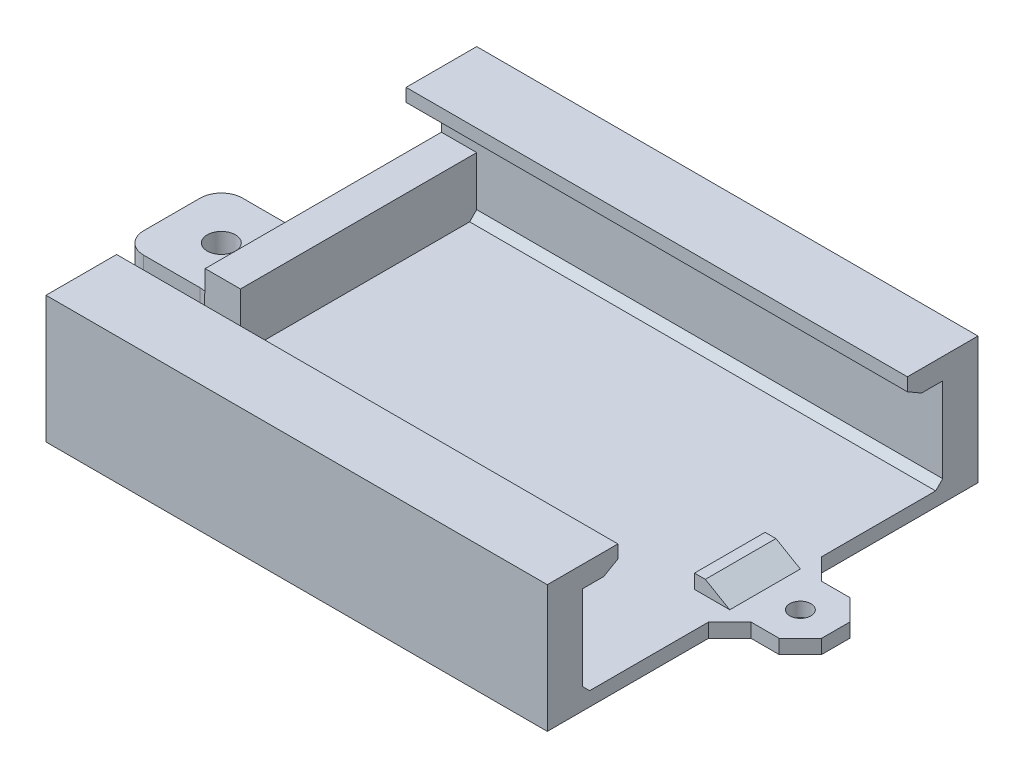
SolidWorks part; units mm, degrees
ref_plane "Front Plane" through (0, 0, 0) normal (0, 0, 1) x (1, 0, 0)
ref_plane "Top Plane" through (0, 0, 0) normal (0, 1, 0) x (1, 0, 0)
ref_plane "Right Plane" through (0, 0, 0) normal (1, 0, 0) x (0, 0, -1)
sketch "Sketch1" plane through (0, 0, 0) normal (0, 1, 0) x (1, 0, 0)
  line L1 (-30.5, -25.5) -> (30.5, -25.5)
  line L2 (-30.5, -25.5) -> (-30.5, 25.5)
  line L3 (-30.5, 25.5) -> (30.5, 25.5)
  line L4 (30.5, -25.5) -> (30.5, 25.5)
  line L5 (-30.5, -25.5) -> (30.5, 25.5) construction
  line L6 (-30.5, 25.5) -> (30.5, -25.5) construction
  line L7 (-35.5, -30.5) -> (35.5, -30.5)
  line L8 (-35.5, -30.5) -> (-35.5, 30.5)
  line L9 (-35.5, 30.5) -> (35.5, 30.5)
  line L10 (35.5, -30.5) -> (35.5, 30.5)
  line L11 (-35.5, -30.5) -> (35.5, 30.5) construction
  line L12 (-35.5, 30.5) -> (35.5, -30.5) construction
  point P0 (0, 0)
  point P6 (0, 0)
  dimension "D1" = 61
  dimension "D2" = 51
  dimension "D3" = 5
  dimension "D4" = 5
extrude "Boss-Extrude1" add sketch "Sketch1" along normal blind 16
sketch "Sketch2" plane through (0, 0, 0) normal (0, -1, 0) x (1, 0, 0)
  line L1 (-35.5, -30.5) -> (35.5, -30.5)
  line L2 (-35.5, -30.5) -> (-35.5, 30.5)
  line L3 (-35.5, 30.5) -> (35.5, 30.5)
  line L4 (35.5, -30.5) -> (35.5, 30.5)
  line L5 (-35.5, -30.5) -> (35.5, 30.5) construction
  line L6 (-35.5, 30.5) -> (35.5, -30.5) construction
  point P0 (0, 0)
extrude "Boss-Extrude2" add sketch "Sketch2" along normal blind 2
sketch "Sketch3" plane through (-30.5, 0, 0) normal (1, 0, 0) x (0, 0, -1)
  line L0 (25.5, 16) -> (-25.5, 16) construction
  line L1 (-19.8095, 16) -> (-7.9597, 16)
  line L2 (-19.8095, 16) -> (-19.8095, 0)
  line L3 (-19.8095, 0) -> (-7.9597, 0)
  line L4 (-7.9597, 16) -> (-7.9597, 0)
  line L5 (25.5, 0) -> (-25.5, 0) construction
extrude "Cut-Extrude1" cut sketch "Sketch3" against normal blind 12
fillet "Fillet1" radius 3 2 edges at (-33, 0, 19.8095) (-33, 0, 7.9597)
sketch "Sketch4" plane through (30.5, 0, 0) normal (-1, 0, 0) x (0, 0, 1)
  line L0 (25.5, 16) -> (-25.5, 16) construction
  line L1 (-25.5, 0) -> (-10.5, 0)
  line L2 (-25.5, 0) -> (-25.5, 16)
  line L3 (-25.5, 16) -> (-10.5, 16)
  line L4 (-10.5, 0) -> (-10.5, 16)
  line L6 (25.5, 0) -> (10.5, 0)
  line L7 (25.5, 0) -> (25.5, 16)
  line L8 (25.5, 16) -> (10.5, 16)
  line L9 (10.5, 0) -> (10.5, 16)
  dimension "D1" = 15
  dimension "D2" = 15
extrude "Cut-Extrude2" cut sketch "Sketch4" against normal blind 12
sketch "Sketch5" plane through (30.5, 0, 0) normal (-1, 0, 0) x (0, 0, 1)
  line L0 (10.5, 16) -> (10.5, 0) construction
  line L1 (-10.5, 16) -> (10.5, 16)
  line L2 (-10.5, 16) -> (-10.5, 8)
  line L3 (-10.5, 8) -> (10.5, 8)
  line L4 (10.5, 16) -> (10.5, 8)
extrude "Cut-Extrude3" cut sketch "Sketch5" against normal blind 12
sketch "Sketch6" plane through (-30.5, 0, 0) normal (1, 0, 0) x (0, 0, -1)
  line L0 (25.5, 16) -> (25.5, 0) construction
  line L1 (-25.5, 16) -> (25.5, 16)
  line L2 (-25.5, 16) -> (-25.5, 8)
  line L3 (-25.5, 8) -> (25.5, 8)
  line L4 (25.5, 16) -> (25.5, 8)
extrude "Cut-Extrude4" cut sketch "Sketch6" against normal blind 12
chamfer "Chamfer1" distance 1 angle 45 2 edges at (2.5, 0, 25.5) (2.5, 0, -25.5)
sketch "Sketch8" plane through (30.5, 0, 0) normal (-1, 0, 0) x (0, 0, 1)
  line L1 (10.5, 8) -> (-10.5, 8)
  line L2 (10.5, 8) -> (10.5, 0)
  line L3 (10.5, 0) -> (-10.5, 0)
  line L4 (-10.5, 8) -> (-10.5, 0)
extrude "Cut-Extrude5" cut sketch "Sketch8" against normal blind 14
sketch "Sketch9" plane through (0, 0, -25.5) normal (0, 0, 1) x (1, 0, 0)
  line L0 (35.5, 16) -> (35.5, 1) construction
  line L1 (-35.5, 16) -> (35.5, 16)
  line L2 (-35.5, 16) -> (-35.5, 13)
  line L3 (-35.5, 13) -> (35.5, 13)
  line L4 (35.5, 16) -> (35.5, 13)
  line L5 (35.5, 0) -> (-30.5, 0) construction
  dimension "D1" = 13
extrude "Boss-Extrude4" add sketch "Sketch9" along normal blind 5
chamfer "Chamfer3" distance 2 angle 30 1 edges at (0, 13, -20.5) first distance on face at (0, 13, -23)
sketch "Sketch10" plane through (0, 0, 25.5) normal (0, 0, -1) x (-1, 0, 0)
  line L0 (-35.5, 1) -> (-35.5, 16) construction
  line L1 (35.5, 16) -> (-35.5, 16)
  line L2 (35.5, 16) -> (35.5, 13)
  line L3 (35.5, 13) -> (-35.5, 13)
  line L4 (-35.5, 16) -> (-35.5, 13)
  line L5 (30.5, 0) -> (-35.5, 0) construction
  dimension "D1" = 13
extrude "Boss-Extrude5" add sketch "Sketch10" along normal blind 5
chamfer "Chamfer4" distance 2 angle 30 1 edges at (0, 13, 20.5) first distance on face at (0, 13, 23)
sketch "Sketch11" plane through (0, 0, 0) normal (0, 1, 0) x (1, 0, 0)
  line L0 (35.5, 24.5) -> (35.5, -24.5) construction
  line L1 (35.5, -4.6573) -> (30.5, -4.6573)
  line L2 (35.5, -4.6573) -> (35.5, 5.3427)
  line L3 (35.5, 5.3427) -> (30.5, 5.3427)
  line L4 (30.5, -4.6573) -> (30.5, 5.3427)
  point P6 (35.5, 0.3427)
  dimension "D1" = 5
  dimension "D2" = 5
extrude "Boss-Extrude6" add sketch "Sketch11" along normal blind 2
chamfer "Chamfer5" distance 2 angle 60 1 edges at (35.5, 2, -0.3427) first distance on face at (35.5, 7.3155, -0.0685)
sketch "Sketch12" plane through (-35.5, 0, 0) normal (-1, 0, 0) x (0, 0, 1)
  line L0 (30.5, -2) -> (-30.5, -2) construction
  line L1 (-8.3327, -2) -> (5.6673, -2)
  line L2 (-8.3327, -2) -> (-8.3327, 3)
  line L3 (-8.3327, 3) -> (5.6673, 3)
  line L4 (5.6673, -2) -> (5.6673, 3)
  point P6 (-1.3327, -2)
  dimension "D1" = 7
  dimension "D2" = 5
extrude "Boss-Extrude7" add sketch "Sketch12" along normal blind 14
chamfer "Chamfer6" distance 2 angle 45 1 edges at (-35.5, 3, -1.3327)
sketch "Sketch13" plane through (0, 3, 0) normal (0, 1, 0) x (1, 0, 0)
  line L0 (-49.5, -5.6673) -> (-49.5, 8.3327) construction
  circle A0 centre (-42.5, 1.3327) radius 2
  dimension "D1" = 4
  dimension "D2" = 7
extrude "Cut-Extrude6" cut sketch "Sketch13" against normal blind 14
fillet "Fillet2" radius 3 2 edges at (-49.5, 0.5, -8.3327) (-49.5, 0.5, 5.6673)
sketch "Sketch14" plane through (35.5, 0, 0) normal (1, 0, 0) x (0, 0, -1)
  line L0 (30.5, -2) -> (-30.5, -2) construction
  line L1 (-4.6573, 0) -> (5.3427, 0)
  line L2 (-4.6573, 0) -> (-4.6573, -2)
  line L3 (-4.6573, -2) -> (5.3427, -2)
  line L4 (5.3427, 0) -> (5.3427, -2)
extrude "Boss-Extrude8" add sketch "Sketch14" along normal blind 10
sketch "Sketch15" plane through (0, 0, 0) normal (0, 1, 0) x (1, 0, 0)
  line L0 (45.5, 5.3427) -> (45.5, -4.6573) construction
  circle A0 centre (40.5, 0.3427) radius 1.5
  dimension "D1" = 3
  dimension "D2" = 5
extrude "Cut-Extrude7" cut sketch "Sketch15" against normal blind 10
chamfer "Chamfer7" distance 3 angle 45 2 edges at (45.5, -1, -5.3427) (45.5, -1, 4.6573)
chamfer "Chamfer8" distance 3 angle 45 2 edges at (35.5, -1, -5.3427) (35.5, -1, 4.6573)
fillet "Fillet3" radius 3 2 edges at (-35.5, 1.5, 5.6673) (-35.5, 1.5, -8.3327)
